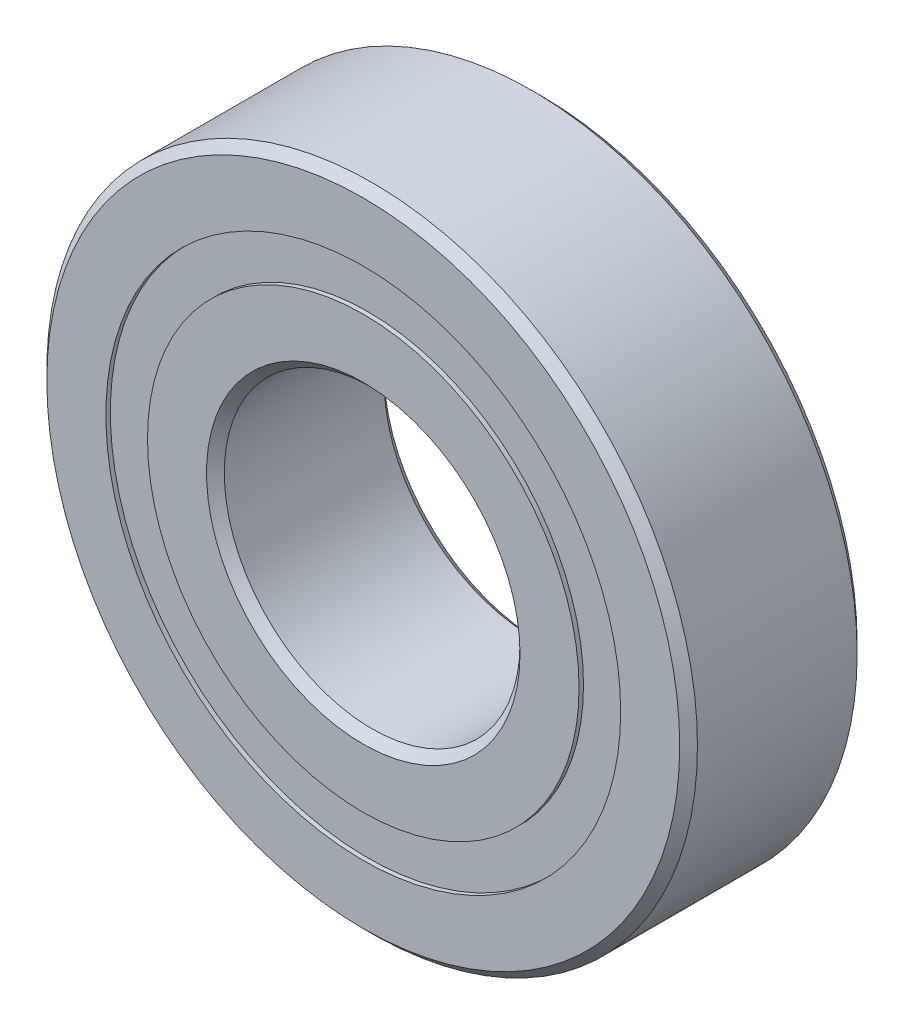
SolidWorks part; units mm, degrees
ref_plane "Front Plane" through (0, 0, 0) normal (0, 0, 1) x (1, 0, 0)
ref_plane "Top Plane" through (0, 0, 0) normal (0, 1, 0) x (1, 0, 0)
ref_plane "Right Plane" through (0, 0, 0) normal (1, 0, 0) x (0, 0, -1)
sketch "Sketch1" plane through (0, 0, 0) normal (1, 0, 0) x (0, 0, -1)
  line L0 (-3, 0) -> (3, 0) construction
  line L1 (0, 11) -> (0, -11) construction
  line L2 (2.7, 11) -> (-2.7, 11)
  line L3 (-2.7, 11) -> (-3, 10.7)
  line L4 (-3, 10.7) -> (-3, 8.7033)
  line L5 (-3, 8.7033) -> (-1.3333, 8.7033)
  line L6 (3, 8.7033) -> (1.3333, 8.7033)
  line L7 (3, 10.7) -> (3, 8.7033)
  line L8 (2.7, 11) -> (3, 10.7)
  line L9 (0, 11) -> (0, 8) construction
  line L10 (0, 8) -> (0, 5) construction
  arc A0 (-1.3333, 8.7033) -> (1.3333, 8.7033) centre (0, 8) cw
  point P14 (0, 5)
  dimension "Width" = 6
  dimension "OD" = 22
  dimension "D1" = 45
  dimension "D2" = 0.3
  dimension "Shaft Dia" = 10
  dimension "D3" = 2.6667
  dimension "D4" = 0.7033
revolve "Revolve1" add sketch "Sketch1" angle 360 about L0
sketch "Sketch3" plane through (0, 0, 0) normal (1, 0, 0) x (0, 0, -1)
  line L0 (-3, 7.2967) -> (-1.3333, 7.2967)
  line L1 (0, 11) -> (0, -11) construction
  line L2 (-3, 10.7) -> (-3, 8.7033) construction
  line L3 (-3, 7.2967) -> (-3, 5.3)
  line L4 (-2.7, 11) -> (-3, 10.7) construction
  line L5 (-3, 5.3) -> (-2.7, 5)
  line L6 (-2.7, 5) -> (2.7, 5)
  line L7 (2.7, 11) -> (2.7, -11) construction
  line L8 (2.7, 5) -> (3, 5.3)
  line L9 (3, -10.7) -> (3, 10.7) construction
  line L10 (3, 5.3) -> (3, 7.2967)
  line L11 (3, 7.2967) -> (1.3333, 7.2967)
  line L13 (2.7, 11) -> (3, 10.7) construction
  arc A0 (1.3333, 8.7033) -> (-1.3333, 8.7033) centre (0, 8) ccw construction
  arc A1 (1.3333, 7.2967) -> (-1.3333, 7.2967) centre (0, 8) cw
revolve "Revolve3" add sketch "Sketch3" angle 360 about L0
sketch "Sketch4" plane through (0, 0, 0) normal (1, 0, 0) x (0, 0, -1)
  line L0 (-1.5074, 8) -> (1.5074, 8)
  arc A2 (-1.5074, 8) -> (1.5074, 8) centre (0, 8) cw
  arc A3 (1.3333, 8.7033) -> (-1.3333, 8.7033) centre (0, 8) ccw construction
revolve "Revolve4" add sketch "Sketch4" angle 360 about L0
ref_axis "Axis1" through (0, 0, -3) along (0, 0, 1)
pattern_circular "CirPattern1" count 12 every 30 about axis through (0, 0, -3) along (0, 0, 1) of bodies 104
sketch "Sketch5" plane through (0, 0, 0) normal (1, 0, 0) x (0, 0, -1)
  line L0 (-3, 8.7033) -> (-1.3333, 8.7033) construction
  line L1 (-2.85, 8.7033) -> (-1.5074, 8.7033)
  line L2 (-2.85, 8.7033) -> (-2.85, 7.2967)
  line L3 (-2.85, 7.2967) -> (-1.5074, 7.2967)
  line L4 (-1.5074, 8.7033) -> (-1.5074, 7.2967)
  line L5 (-3, 7.2967) -> (-1.3333, 7.2967) construction
  line L6 (3, 8.7033) -> (1.3333, 8.7033) construction
  line L7 (2.85, 8.7033) -> (1.5074, 8.7033)
  line L8 (2.85, 8.7033) -> (2.85, 7.2967)
  line L9 (2.85, 7.2967) -> (1.5074, 7.2967)
  line L10 (1.5074, 8.7033) -> (1.5074, 7.2967)
  line L11 (3, 7.2967) -> (1.3333, 7.2967) construction
  line L12 (-2.7, 11) -> (-3, 10.7) construction
  point P18 (-2.85, 10.85)
revolve "Revolve5" add sketch "Sketch5" angle 360 about L0
equation "\"D2@Sketch1\" = \"Width@Sketch1\"*.05"
equation "\"D3@Sketch1\" = \"Width@Sketch1\"/2.25"
equation "\"D4@Sketch1\" = (((\"OD@Sketch1\"-\"Width@Sketch1\")/2)/3.25)/3.5"
equation "\"D2@CirPattern1\" = 360/\"Balls@CirPattern1\""
